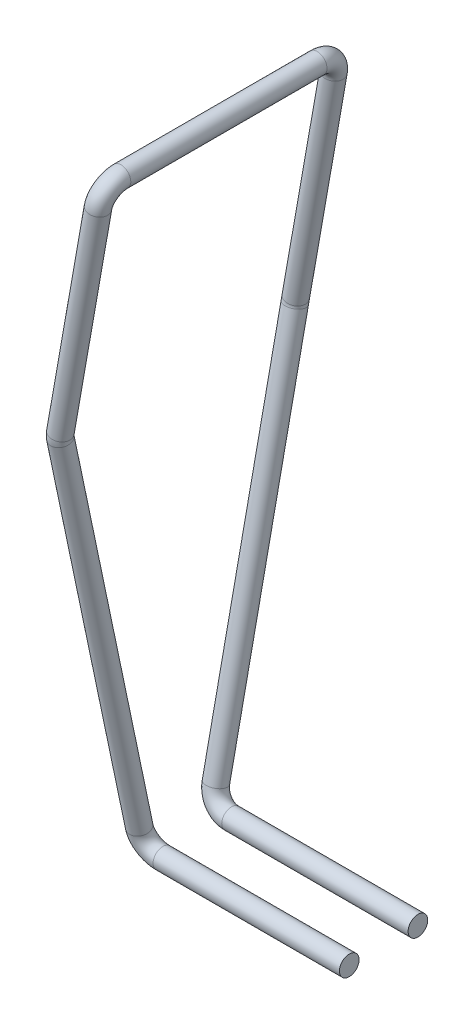
SolidWorks part; units mm, degrees
ref_plane "Front Plane" through (0, 0, 0) normal (0, 0, 1) x (1, 0, 0)
ref_plane "Top Plane" through (0, 0, 0) normal (0, 1, 0) x (1, 0, 0)
ref_plane "Right Plane" through (0, 0, 0) normal (1, 0, 0) x (0, 0, -1)
sketch "Sketch2" plane through (0, 0, 0) normal (1, 0, 0) x (0, 0, -1)
  line L0 (0, 0) -> (0, 0.5916) construction
  circle A0 centre (-0.35, 0) radius 0.1
  circle A1 centre (0.35, 0) radius 0.1 construction
  dimension "D1" = 0.7
  dimension "D2" = 0.2
sketch3d "3DSketch1"
  line L0 (0, 0, 0.35) -> (-1.9, 0, 0.35)
  line L1 (0, 0, -0.35) -> (-1.9, 0, -0.35)
  line L2 (-2.1, 0.1957, 0.391) -> (-2.1, 4.027, 1.1944)
  line L3 (-2.1, 0.1957, -0.391) -> (-2.1, 4.027, -1.1944)
  line L4 (-2.0953, 4.0803, 1.2) -> (-1.7115, 6.2566, 1.2)
  line L5 (-1.6768, 6.4536, 1) -> (-1.6768, 6.4536, -1)
  line L6 (-2.1, 4.0536, 1.2) -> (-2.1, 6.4536, 1.2) construction
  line L7 (-1.7115, 6.2566, -1.2) -> (-2.0953, 4.0803, -1.2)
  line L8 (-1.6768, 6.4536, 0) -> (-2.8148, 0, 0) construction
  line L9 (0, 0, 0) -> (-2.8148, 0, 0) construction
  arc A0 (-1.9, 0, -0.35) -> (-2.1, 0.1957, -0.391) centre (-1.9, 0.1957, -0.391) ccw
  arc A1 (-1.9, 0, 0.35) -> (-2.1, 0.1957, 0.391) centre (-1.9, 0.1957, 0.391) ccw
  arc A2 (-2.1, 4.027, -1.1944) -> (-2.0953, 4.0803, -1.2) centre (-1.9697, 4.0581, -1.046) ccw
  arc A3 (-2.1, 4.027, 1.1944) -> (-2.0953, 4.0803, 1.2) centre (-1.9697, 4.0581, 1.046) ccw
  arc A4 (-1.7115, 6.2566, -1.2) -> (-1.6768, 6.4536, -1) centre (-1.7115, 6.2566, -1) ccw
  arc A5 (-1.7115, 6.2566, 1.2) -> (-1.6768, 6.4536, 1) centre (-1.7115, 6.2566, 1) ccw
  point P13 (-2.1, 0, -0.35)
  point P14 (-1.9, 0.1547, -0.5868)
  point P17 (-2.1, 0, 0.35)
  point P18 (-1.9, 0.2368, 0.1953)
  point P21 (-2.1, 4.0536, -1.2)
  point P22 (-1.818, 4.0314, -1.1735)
  point P25 (-2.1, 4.0536, 1.2)
  point P27 (-2.1214, 4.0849, 0.9184)
  point P30 (-1.6768, 6.4536, -1.2)
  point P31 (-1.5146, 6.2219, -1)
  point P34 (-1.6768, 6.4536, 1.2)
  point P35 (-1.9085, 6.2913, 1)
  dimension "D7" = 0.2
  dimension "D8" = 0.2
  dimension "D9" = 0.2
  dimension "D5" = 6.5
  dimension "D1" = 2.1
  dimension "D2" = 10
  dimension "D3" = 2.4
  dimension "D4" = 2.4
sweep "Sweep2" add profiles "Sketch2" path "3DSketch1"
